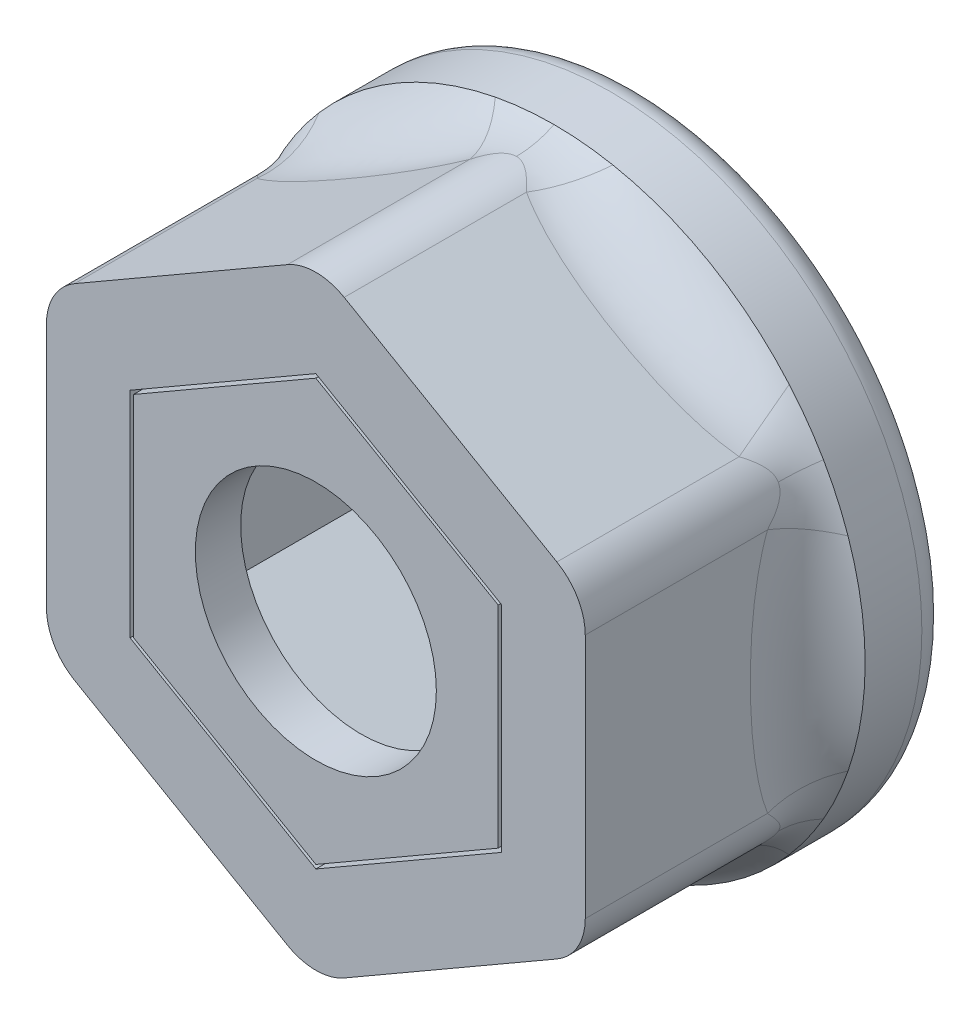
SolidWorks part; units mm, degrees
ref_plane "Front Plane" through (0, 0, 0) normal (0, 0, 1) x (1, 0, 0)
ref_plane "Top Plane" through (0, 0, 0) normal (0, 1, 0) x (1, 0, 0)
ref_plane "Right Plane" through (0, 0, 0) normal (1, 0, 0) x (0, 0, -1)
sketch "Sketch1" plane through (0, 0, 0) normal (0, 0, 1) x (1, 0, 0)
  line L1 (0, -7.5633) -> (6.55, -3.7816)
  line L2 (6.55, -3.7816) -> (6.55, 3.7816)
  line L3 (6.55, 3.7816) -> (0, 7.5633)
  line L4 (0, 7.5633) -> (-6.55, 3.7816)
  line L5 (-6.55, 3.7816) -> (-6.55, -3.7816)
  line L6 (-6.55, -3.7816) -> (0, -7.5633)
  line L7 (0, -10.9697) -> (9.5, -5.4848) construction
  line L8 (9.5, -5.4848) -> (9.5, 5.4848) construction
  line L9 (9.5, 5.4848) -> (0, 10.9697) construction
  line L10 (0, 10.9697) -> (-9.5, 5.4848) construction
  line L11 (-9.5, 5.4848) -> (-9.5, -5.4848) construction
  line L12 (-9.5, -5.4848) -> (0, -10.9697) construction
  circle A0 centre (0, 0) radius 6.55 construction
  circle A1 centre (0, 0) radius 10.9697
  circle A2 centre (0, 0) radius 9.5 construction
  dimension "D1" = 13.1
  dimension "D2" = 19
extrude "Boss-Extrude1" add sketch "Sketch1" along normal blind 6.8
sketch "Sketch7" plane through (0, 0, 6.8) normal (0, 0, 1) x (1, 0, 0)
  circle A0 centre (0, 0) radius 4.5
  circle A1 centre (0, 0) radius 10.9697 construction
  circle A2 centre (0, 0) radius 10.9697
  dimension "D1" = 9
extrude "Boss-Extrude2" add sketch "Sketch7" along normal blind 1.6
sketch "Sketch9" plane through (0, 0, 0) normal (0, 0, -1) x (-1, 0, 0)
  circle A1 centre (0, 0) radius 10.9697 construction
  circle A2 centre (0, 0) radius 10.9697
extrude "Boss-Extrude3" add sketch "Sketch9" along normal blind 3
sketch "Sketch10" plane through (0, 0, 0) normal (0, 0, 1) x (1, 0, 0)
  line L1 (0, -10.9697) -> (9.5, -5.4848)
  line L2 (9.5, -5.4848) -> (9.5, 5.4848)
  line L3 (9.5, 5.4848) -> (0, 10.9697)
  line L4 (0, 10.9697) -> (-9.5, 5.4848)
  line L5 (-9.5, 5.4848) -> (-9.5, -5.4848)
  line L6 (-9.5, -5.4848) -> (0, -10.9697)
  circle A0 centre (0, 0) radius 9.5 construction
  circle A1 centre (0, 0) radius 10.9697 construction
  circle A2 centre (0, 0) radius 10.9697
extrude "Cut-Extrude2" cut sketch "Sketch10" along normal up to next (8.4 mm away) contours L5 A2 | L4 A2 | L3 A2 | L2 A2 | L1 A2 | L6 A2 region at (-5.0457, -8.7394, 0) region at (5.0457, -8.7394, 0) region at (10.0914, 0, 0) region at (-10.0914, 0, 0) region at (5.0457, 8.7394, 0) region at (-5.0457, 8.7394, 0) body kept at (9.5, -5.4848, 0)
fillet "Fillet6" radius 2 6 edges at (0, 10.9697, 4.2) (-9.5, 5.4848, 4.2) (-9.5, -5.4848, 4.2) (0, -10.9697, 4.2) (9.5, -5.4848, 4.2) (9.5, 5.4848, 4.2)
fillet "Fillet7" radius 3 6 edges at (9.5, 0, 0) (4.75, -8.2272, 0) (-4.75, -8.2272, 0) (-9.5, 0, 0) (-4.75, 8.2272, 0) (4.75, 8.2272, 0)
fillet "Fillet8" radius 1 1 edges at (-10.9697, 0, -3)
sketch "Sketch11" plane through (0, 0, 8.4) normal (0, 0, 1) x (1, 0, 0)
  line L12 (0, -7.5633) -> (6.55, -3.7816)
  line L13 (-6.55, -3.7816) -> (0, -7.5633)
  line L14 (-6.55, 3.7816) -> (-6.55, -3.7816)
  line L15 (0, 7.5633) -> (-6.55, 3.7816)
  line L16 (6.55, 3.7816) -> (0, 7.5633)
  line L17 (6.55, -3.7816) -> (6.55, 3.7816)
  line L18 (0, -7.5633) -> (6.55, -3.7816)
  line L19 (-6.55, -3.7816) -> (0, -7.5633)
  line L20 (-6.55, 3.7816) -> (-6.55, -3.7816)
  line L21 (0, 7.5633) -> (-6.55, 3.7816)
  line L22 (6.55, 3.7816) -> (0, 7.5633)
  line L23 (6.55, -3.7816) -> (6.55, 3.7816)
  dimension "D1" = 0
extrude "Cut-Extrude3" cut sketch "Sketch11" against normal up to next
sketch "Sketch12" plane through (0, 0, 8.4) normal (0, 0, 1) x (1, 0, 0)
  line L0 (-6.55, 3.7816) -> (-6.55, -3.7816) construction
  line L1 (0, 7.5633) -> (-6.55, 3.7816) construction
  line L2 (6.55, 3.7816) -> (0, 7.5633) construction
  line L3 (6.55, -3.7816) -> (6.55, 3.7816) construction
  line L4 (0, -7.5633) -> (6.55, -3.7816) construction
  line L5 (-6.55, -3.7816) -> (0, -7.5633) construction
  line L7 (-6.55, -3.7816) -> (0, -7.5633) construction
  line L8 (0, -7.5633) -> (6.55, -3.7816) construction
  line L9 (6.55, -3.7816) -> (6.55, 3.7816) construction
  line L10 (6.55, 3.7816) -> (0, 7.5633) construction
  line L11 (0, 7.5633) -> (-6.55, 3.7816) construction
  line L12 (-6.55, 3.7816) -> (-6.55, -3.7816) construction
  line L13 (-6.43, 3.7124) -> (-6.43, -3.7124)
  line L14 (-6.43, -3.7124) -> (0, -7.4247)
  line L15 (0, -7.4247) -> (6.43, -3.7124)
  line L16 (6.43, -3.7124) -> (6.43, 3.7124)
  line L17 (6.43, 3.7124) -> (0, 7.4247)
  line L18 (0, 7.4247) -> (-6.43, 3.7124)
  circle A0 centre (0, 0) radius 4.25
  dimension "D2" = 8.5
  dimension "D1" = 0.12
extrude "Boss-Extrude4" add sketch "Sketch12" against normal blind 1.6 separate body
